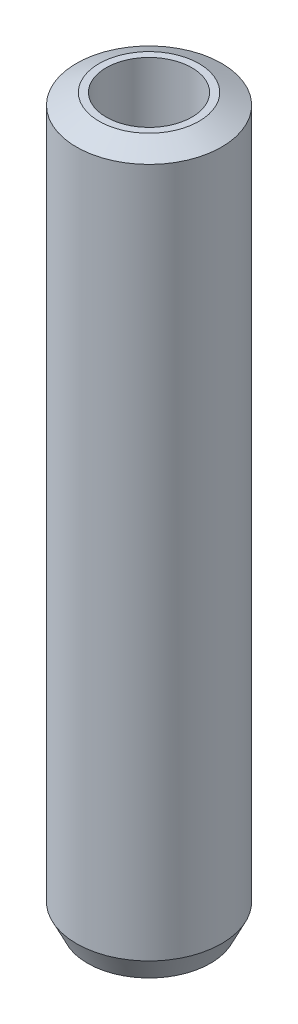
SolidWorks part; units mm, degrees
ref_plane "Front Plane" through (0, 0, 0) normal (0, 0, 1) x (1, 0, 0)
ref_plane "Top Plane" through (0, 0, 0) normal (0, 1, 0) x (1, 0, 0)
ref_plane "Right Plane" through (0, 0, 0) normal (1, 0, 0) x (0, 0, -1)
sketch "Sketch1" plane through (0, 0, 0) normal (0, 1, 0) x (1, 0, 0)
  circle A0 centre (0, 0) radius 22.5
  dimension "SHAFT_OD" = 45
extrude "Boss-Extrude1" add sketch "Sketch1" along normal blind 224.32
sketch "Sketch2" plane through (0, 0, 0) normal (0, 1, 0) x (1, 0, 0)
  circle A0 centre (0, 0) radius 13.288
  dimension "BORE_D" = 26.5759
extrude "Cut-Extrude1" cut sketch "Sketch2" along normal through all
chamfer "Chamfer1" distance 3.4286 angle 63.89 2 edges at (0, 224.32, 22.5) (0, 0, 22.5) first distance on face at (0, 224.32, 22.5) first distance on face at (0, 0, 13.288)
